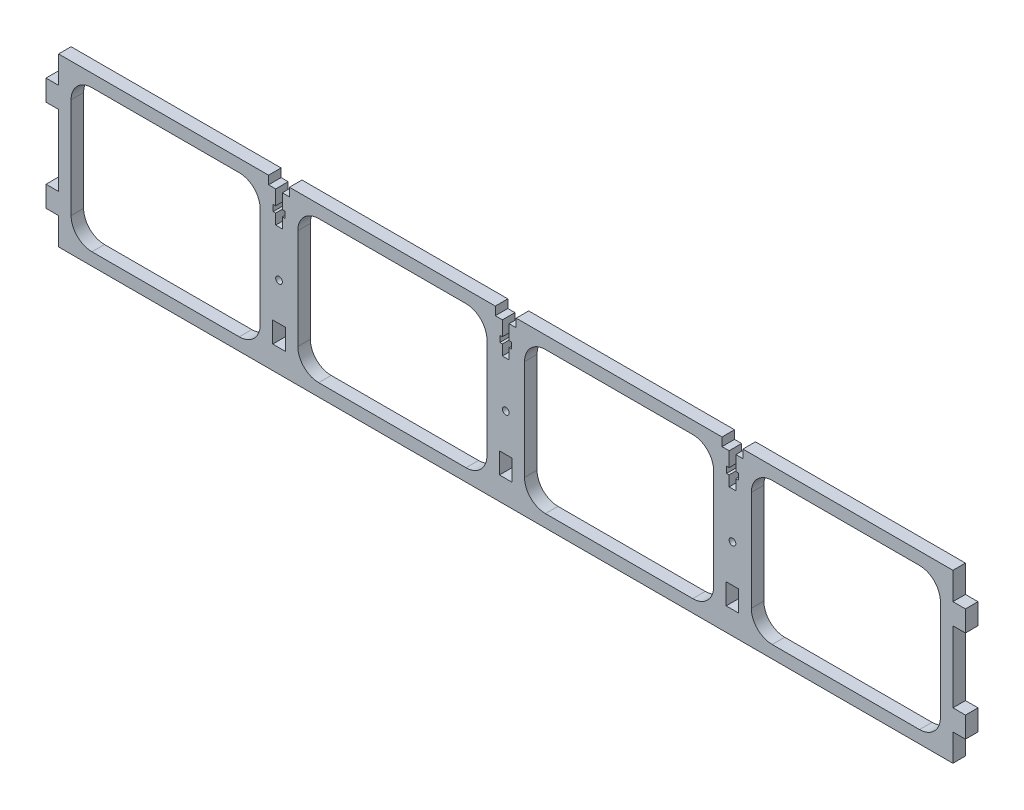
SolidWorks part; units mm, degrees
ref_plane "Front Plane" through (0, 0, 0) normal (0, 0, 1) x (1, 0, 0)
ref_plane "Top Plane" through (0, 0, 0) normal (0, 1, 0) x (1, 0, 0)
ref_plane "Right Plane" through (0, 0, 0) normal (1, 0, 0) x (0, 0, -1)
sketch "Sketch1" plane through (0, 0, 0) normal (0, 0, 1) x (1, 0, 0)
  line L1 (-214, -40) -> (214, -40)
  line L2 (-214, -40) -> (-214, 40)
  line L3 (-214, 40) -> (214, 40)
  line L4 (214, -40) -> (214, 40)
  line L5 (-214, -40) -> (214, 40) construction
  line L6 (-214, 40) -> (214, -40) construction
  point P0 (0, 0)
  dimension "D1" = 428
  dimension "D2" = 80
extrude "Boss-Extrude1" add sketch "Sketch1" along normal blind 6
sketch "Sketch2" plane through (0, 0, 6) normal (0, 0, 1) x (1, 0, 0)
  line L0 (-117.5, -42) -> (-117.5, -29) construction
  line L1 (-208, 40) -> (-208, -40) construction
  line L2 (-214, -34) -> (214, -34) construction
  line L3 (-214, -40) -> (214, -40) construction
  line L8 (214, -40) -> (214, 40)
  line L9 (214, 40) -> (-214, 40)
  line L10 (-214, 40) -> (-214, -40)
  line L11 (-214, -40) -> (214, -40)
  line L12 (214, -40) -> (214, 40) construction
  line L13 (214, 40) -> (-214, 40)
  line L14 (-214, 40) -> (-214, -40) construction
  line L15 (-208, -40) -> (214, -40) construction
  line L16 (-111.5, -42) -> (-111.5, -29) construction
  line L17 (-111.5, -42) -> (-111.5, -29) construction
  line L18 (-117.5, -24) -> (-117.5, 24)
  line L19 (-198, -34) -> (-127.5, -34)
  line L20 (-208, 24) -> (-208, -24)
  line L21 (-127.5, 34) -> (-198, 34)
  arc A0 (-198, 34) -> (-208, 24) centre (-198, 24) ccw
  arc A1 (-127.5, 34) -> (-117.5, 24) centre (-127.5, 24) cw
  arc A2 (-117.5, -24) -> (-127.5, -34) centre (-127.5, -24) cw
  arc A3 (-198, -34) -> (-208, -24) centre (-198, -24) cw
  dimension "D6" = 10
  dimension "D5" = 6
  dimension "D1" = 0
  dimension "D2" = 6
  dimension "D3" = 6
  dimension "D4" = 6
extrude "Cut-Extrude1" cut sketch "Sketch2" against normal up to next contours L18 L21 L20 L19 region at (-162.75, 0, 6)
pattern_linear "LPattern1" count 4 spacing 108.5 along (1, 0, 0) of "Cut-Extrude1"
sketch "Sketch3" plane through (0, 0, 0) normal (0, 0, -1) x (-1, 0, 0)
  line L8 (-111.5, -29) -> (-111.5, -19) construction
  line L9 (-111.5, -19) -> (-105.5, -19) construction
  line L10 (-105.5, -19) -> (-105.5, -29) construction
  line L11 (-105.5, -29) -> (-111.5, -29) construction
  line L24 (-111.5, -29) -> (-111.5, -19)
  line L25 (-111.5, -19) -> (-105.5, -19)
  line L26 (-105.5, -19) -> (-105.5, -29)
  line L27 (-105.5, -29) -> (-111.5, -29)
  line L44 (-3, -29) -> (-3, -19) construction
  line L45 (-3, -19) -> (3, -19) construction
  line L46 (3, -19) -> (3, -29) construction
  line L47 (3, -29) -> (-3, -29) construction
  line L52 (-3, -29) -> (-3, -19)
  line L53 (-3, -19) -> (3, -19)
  line L54 (3, -19) -> (3, -29)
  line L55 (3, -29) -> (-3, -29)
  line L60 (105.5, -29) -> (105.5, -19) construction
  line L61 (105.5, -19) -> (111.5, -19) construction
  line L62 (111.5, -19) -> (111.5, -29) construction
  line L63 (111.5, -29) -> (105.5, -29) construction
  line L68 (105.5, -29) -> (105.5, -19)
  line L69 (105.5, -19) -> (111.5, -19)
  line L70 (111.5, -19) -> (111.5, -29)
  line L71 (111.5, -29) -> (105.5, -29)
  circle A3 centre (108.5, -1) radius 1.6 construction
  circle A4 centre (0, -1) radius 1.6 construction
  circle A5 centre (-108.5, -1) radius 1.6 construction
  circle A6 centre (108.5, -1) radius 1.6
  circle A7 centre (0, -1) radius 1.6
  circle A8 centre (-108.5, -1) radius 1.6
extrude "Cut-Extrude2" cut sketch "Sketch3" against normal through all
sketch "Sketch4" plane through (0, 0, 0) normal (0, 0, -1) x (-1, 0, 0)
  line L0 (-111.5, 17) -> (-214, 17) construction
  line L1 (-214, -40) -> (-214, 40) construction
  line L2 (-108.5, 0) -> (-214, 0) construction
  line L3 (-220, 21.3321) -> (-220, 40) construction
  line L4 (-214, 17) -> (-220, 17)
  line L5 (-214, 17) -> (-214, 27)
  line L6 (-214, 27) -> (-220, 27)
  line L7 (-220, 17) -> (-220, 27)
  line L9 (-220, -17) -> (-220, -27)
  line L10 (-214, -27) -> (-220, -27)
  line L11 (-214, -17) -> (-214, -27)
  line L12 (-214, -17) -> (-220, -17)
  line L13 (0, 0) -> (0, 40) construction
  line L14 (-214, 40) -> (214, 40) construction
  line L15 (214, -17) -> (220, -17)
  line L16 (214, -17) -> (214, -27)
  line L17 (214, -27) -> (220, -27)
  line L18 (220, -17) -> (220, -27)
  line L19 (220, 17) -> (220, 27)
  line L20 (214, 27) -> (220, 27)
  line L21 (214, 17) -> (214, 27)
  line L22 (214, 17) -> (220, 17)
  point P2 (0, 0)
  point P13 (-108.5, -1)
  dimension "D1" = 34
  dimension "D2" = 10
extrude "Boss-Extrude2" add sketch "Sketch4" against normal blind 6
sketch "Sketch5" plane through (0, 40, 0) normal (0, 1, 0) x (1, 0, 0)
  line L0 (214, -6) -> (-214, -6) construction
  line L1 (-113.5, 0) -> (-103.5, 0)
  line L2 (-113.5, 0) -> (-113.5, -6)
  line L3 (-113.5, -6) -> (-103.5, -6)
  line L4 (-103.5, 0) -> (-103.5, -6)
  line L5 (-113.5, 0) -> (-103.5, -6) construction
  line L6 (-113.5, -6) -> (-103.5, 0) construction
  line L7 (-103.5, -6) -> (-103.5, 0) construction
  line L8 (5, -6) -> (5, 0) construction
  line L9 (-5, 0) -> (5, 0)
  line L10 (-5, 0) -> (-5, -6)
  line L11 (-5, -6) -> (5, -6)
  line L12 (5, 0) -> (5, -6)
  line L13 (-5, 0) -> (5, -6) construction
  line L14 (-5, -6) -> (5, 0) construction
  line L15 (113.5, -6) -> (113.5, 0) construction
  line L16 (103.5, 0) -> (113.5, 0)
  line L17 (103.5, 0) -> (103.5, -6)
  line L18 (103.5, -6) -> (113.5, -6)
  line L19 (113.5, 0) -> (113.5, -6)
  line L20 (103.5, 0) -> (113.5, -6) construction
  line L21 (103.5, -6) -> (113.5, 0) construction
  point P0 (-108.5, -3)
  point P10 (0, -3)
  point P18 (108.5, -3)
extrude "Cut-Extrude3" cut sketch "Sketch5" against normal blind 4
sketch "Sketch6" plane through (0, 0, 0) normal (0, 0, -1) x (-1, 0, 0)
  line L12 (-110.1, 36) -> (-110.1, 29)
  line L13 (-106.9, 36) -> (-110.1, 36)
  line L14 (-106.9, 29) -> (-106.9, 36)
  line L15 (-105.7, 29) -> (-106.9, 29)
  line L16 (-105.7, 26) -> (-105.7, 29)
  line L17 (-106.9, 26) -> (-105.7, 26)
  line L18 (-106.9, 21) -> (-106.9, 26)
  line L19 (-110.1, 21) -> (-106.9, 21)
  line L20 (-110.1, 26) -> (-110.1, 21)
  line L21 (-111.3, 26) -> (-110.1, 26)
  line L22 (-111.3, 29) -> (-111.3, 26)
  line L23 (-110.1, 29) -> (-111.3, 29)
  line L24 (-110.1, 36) -> (-110.1, 29)
  line L25 (-106.9, 36) -> (-110.1, 36)
  line L26 (-106.9, 29) -> (-106.9, 36)
  line L27 (-105.7, 29) -> (-106.9, 29)
  line L28 (-105.7, 26) -> (-105.7, 29)
  line L29 (-106.9, 26) -> (-105.7, 26)
  line L30 (-106.9, 21) -> (-106.9, 26)
  line L31 (-110.1, 21) -> (-106.9, 21)
  line L32 (-110.1, 26) -> (-110.1, 21)
  line L33 (-111.3, 26) -> (-110.1, 26)
  line L34 (-111.3, 29) -> (-111.3, 26)
  line L35 (-110.1, 29) -> (-111.3, 29)
  line L36 (-1.6, 29) -> (-2.8, 29)
  line L37 (-2.8, 29) -> (-2.8, 26)
  line L38 (-2.8, 26) -> (-1.6, 26)
  line L39 (-1.6, 26) -> (-1.6, 21)
  line L40 (-1.6, 21) -> (1.6, 21)
  line L41 (1.6, 21) -> (1.6, 26)
  line L42 (1.6, 26) -> (2.8, 26)
  line L43 (2.8, 26) -> (2.8, 29)
  line L44 (2.8, 29) -> (1.6, 29)
  line L45 (1.6, 29) -> (1.6, 36)
  line L46 (1.6, 36) -> (-1.6, 36)
  line L47 (-1.6, 36) -> (-1.6, 29)
  line L48 (-1.6, 29) -> (-2.8, 29)
  line L49 (-2.8, 29) -> (-2.8, 26)
  line L50 (-2.8, 26) -> (-1.6, 26)
  line L51 (-1.6, 26) -> (-1.6, 21)
  line L52 (-1.6, 21) -> (1.6, 21)
  line L53 (1.6, 21) -> (1.6, 26)
  line L54 (1.6, 26) -> (2.8, 26)
  line L55 (2.8, 26) -> (2.8, 29)
  line L56 (2.8, 29) -> (1.6, 29)
  line L57 (1.6, 29) -> (1.6, 36)
  line L58 (1.6, 36) -> (-1.6, 36)
  line L59 (-1.6, 36) -> (-1.6, 29)
  line L60 (106.9, 36) -> (106.9, 29)
  line L61 (110.1, 36) -> (106.9, 36)
  line L62 (110.1, 29) -> (110.1, 36)
  line L63 (111.3, 29) -> (110.1, 29)
  line L64 (111.3, 26) -> (111.3, 29)
  line L65 (110.1, 26) -> (111.3, 26)
  line L66 (110.1, 21) -> (110.1, 26)
  line L67 (106.9, 21) -> (110.1, 21)
  line L68 (106.9, 26) -> (106.9, 21)
  line L69 (105.7, 26) -> (106.9, 26)
  line L70 (105.7, 29) -> (105.7, 26)
  line L71 (106.9, 29) -> (105.7, 29)
  line L72 (106.9, 36) -> (106.9, 29)
  line L73 (110.1, 36) -> (106.9, 36)
  line L74 (110.1, 29) -> (110.1, 36)
  line L75 (111.3, 29) -> (110.1, 29)
  line L76 (111.3, 26) -> (111.3, 29)
  line L77 (110.1, 26) -> (111.3, 26)
  line L78 (110.1, 21) -> (110.1, 26)
  line L79 (106.9, 21) -> (110.1, 21)
  line L80 (106.9, 26) -> (106.9, 21)
  line L81 (105.7, 26) -> (106.9, 26)
  line L82 (105.7, 29) -> (105.7, 26)
  line L83 (106.9, 29) -> (105.7, 29)
  dimension "D1" = 0
  dimension "D2" = 0
  dimension "D3" = 0
extrude "Cut-Extrude4" cut sketch "Sketch6" against normal up to next
